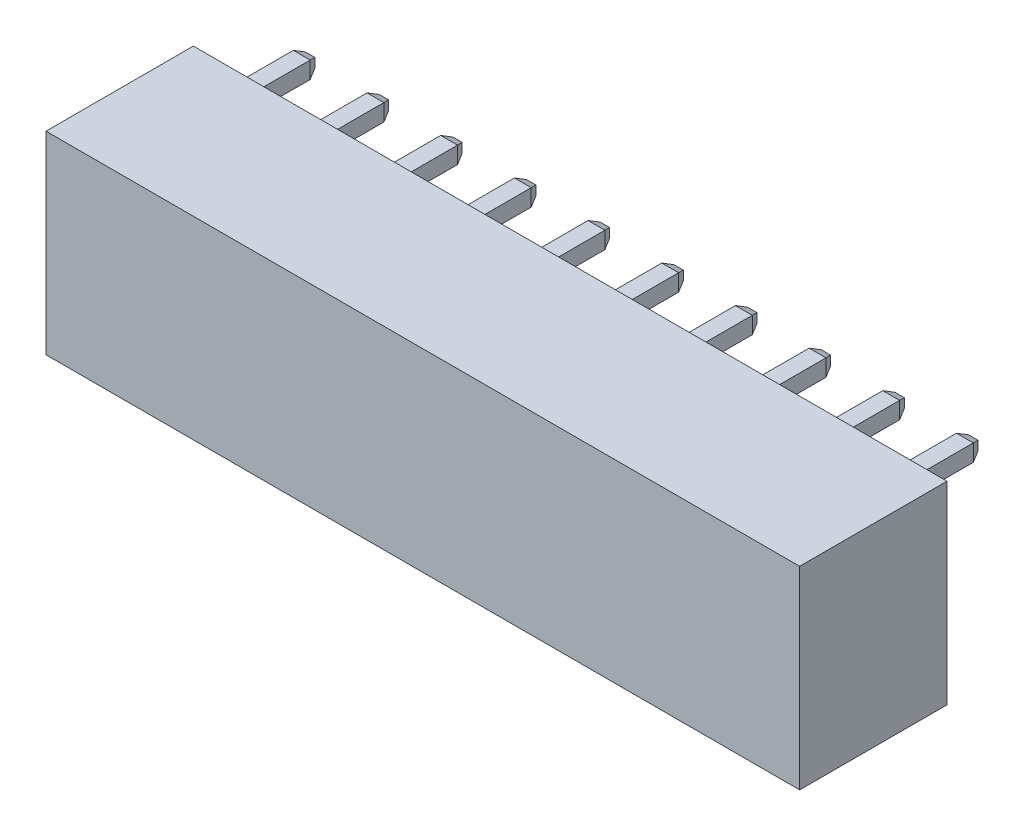
SolidWorks part; units mm, degrees
ref_plane "Спереди" through (0, 0, 0) normal (0, 0, 1) x (1, 0, 0)
ref_plane "Сверху" through (0, 0, 0) normal (0, 1, 0) x (1, 0, 0)
ref_plane "Справа" through (0, 0, 0) normal (1, 0, 0) x (0, 0, -1)
sketch "Эскиз1" plane through (0, 0, 0) normal (0, 0, 1) x (1, 0, 0)
  line L1 (17.9, 9.2) -> (-17.9, 9.2)
  line L2 (17.9, 9.2) -> (17.9, 0)
  line L3 (17.9, 0) -> (-17.9, 0)
  line L4 (-17.9, 9.2) -> (-17.9, 0)
  line L5 (17.9, 9.2) -> (-17.9, 0) construction
  line L6 (17.9, 0) -> (-17.9, 9.2) construction
  point P0 (0, 4.6)
  dimension "D1" = 9.2
  dimension "D2" = 35.8
extrude "Бобышка-Вытянуть1" add sketch "Эскиз1" along normal blind 7
sketch "Эскиз2" plane through (0, 0, 0) normal (0, 0, -1) x (-1, 0, 0)
  line L0 (17.9, 0) -> (-17.9, 0) construction
  line L1 (-16.15, 7.6) -> (-15.35, 7.6)
  line L2 (-16.15, 7.6) -> (-16.15, 8.4)
  line L3 (-16.15, 8.4) -> (-15.35, 8.4)
  line L4 (-15.35, 7.6) -> (-15.35, 8.4)
  line L5 (-16.15, 7.6) -> (-15.35, 8.4) construction
  line L6 (-16.15, 8.4) -> (-15.35, 7.6) construction
  line L7 (-17.9, 0) -> (-17.9, 9.2) construction
  point P0 (-15.75, 8)
  dimension "D1" = 8
  dimension "D2" = 0.8
  dimension "D3" = 2.15
extrude "Бобышка-Вытянуть2" add sketch "Эскиз2" along normal blind 3.4
chamfer "Фаска1" distance 0.4 angle 24 4 edges at (15.75, 8.4, -3.4) (15.35, 8, -3.4) (15.75, 7.6, -3.4) (16.15, 8, -3.4) first distance on face at (15.75, 8.4, -1.7) first distance on face at (15.35, 8, -1.7) first distance on face at (15.75, 7.6, -1.7) first distance on face at (16.15, 8, -1.7)
sketch "Эскиз3" plane through (0, 0, 0) normal (0, -1, 0) x (1, 0, 0)
  line L1 (14.15, 0.8) -> (17.25, 0.8)
  line L2 (14.15, 0.8) -> (14.15, 5)
  line L4 (17.25, 0.8) -> (17.25, 5)
  line L5 (14.15, 0.8) -> (17.25, 5) construction
  line L6 (14.15, 5) -> (17.25, 0.8) construction
  line L7 (-17.9, 0) -> (17.9, 0) construction
  line L9 (17.9, 7) -> (17.9, 0) construction
  line L10 (-17.9, 7) -> (17.9, 7) construction
  line L11 (14.15, 6.5) -> (17.25, 6.5)
  line L12 (14.15, 5) -> (15.15, 5)
  line L13 (15.15, 5) -> (14.15, 6.5)
  line L14 (17.25, 5) -> (16.25, 5)
  line L15 (16.25, 5) -> (17.25, 6.5)
  point P0 (15.7, 2.9)
  point P5 (15.7, 6.5)
  dimension "D1" = 2.2
  dimension "D2" = 0.8
  dimension "D3" = 2
  dimension "D4" = 3.1
  dimension "D5" = 0.5
  dimension "D6" = 1
extrude "Вырез-Вытянуть1" cut sketch "Эскиз3" against normal blind 7
pattern_linear "Линейный массив1" count 10 spacing 3.5 along (-1, 0, 0) of "Бобышка-Вытянуть2", "Фаска1"
pattern_linear "Линейный массив2" count 10 spacing 3.5 along (-1, 0, 0) of "Вырез-Вытянуть1"
sketch "Эскиз4" plane through (0, 7, 0) normal (0, -1, 0) x (1, 0, 0)
  line L0 (16.15, -3) -> (16.15, 0) construction
  line L1 (15.35, 3.4) -> (16.15, 3.4)
  line L2 (15.35, 3.4) -> (15.35, 2.6)
  line L3 (15.35, 2.6) -> (16.15, 2.6)
  line L4 (16.15, 3.4) -> (16.15, 2.6)
  line L5 (15.35, 3.4) -> (16.15, 2.6) construction
  line L6 (15.35, 2.6) -> (16.15, 3.4) construction
  line L7 (15.35, -3) -> (15.35, 0) construction
  line L8 (-17.9, 0) -> (17.9, 0) construction
  point P0 (15.75, 3)
  dimension "D1" = 3
extrude "Бобышка-Вытянуть3" add sketch "Эскиз4" along normal blind 6
chamfer "Фаска2" distance 0.4 angle 24 4 edges at (16.15, 1, 3) (15.75, 1, 3.4) (15.35, 1, 3) (15.75, 1, 2.6) first distance on face at (16.15, 4, 3) first distance on face at (15.75, 4, 3.4) first distance on face at (15.35, 4, 3) first distance on face at (15.75, 4, 2.6)
pattern_linear "Линейный массив3" count 10 spacing 3.5 along (-1, 0, 0) of "Фаска2", "Бобышка-Вытянуть3"
equation "\"n\"= 10"
equation "\"width\"= 3.5 * ( \"n\" - 1 ) + 4.3"
equation "\"D2@Эскиз1\" = 3.5 * ( \"n\" - 1 ) + 4.3"
equation "\"D1@Линейный массив1\"=\"n\""
equation "\"D1@Линейный массив2\"=\"n\""
equation "\"D1@Линейный массив3\"=\"n\""
